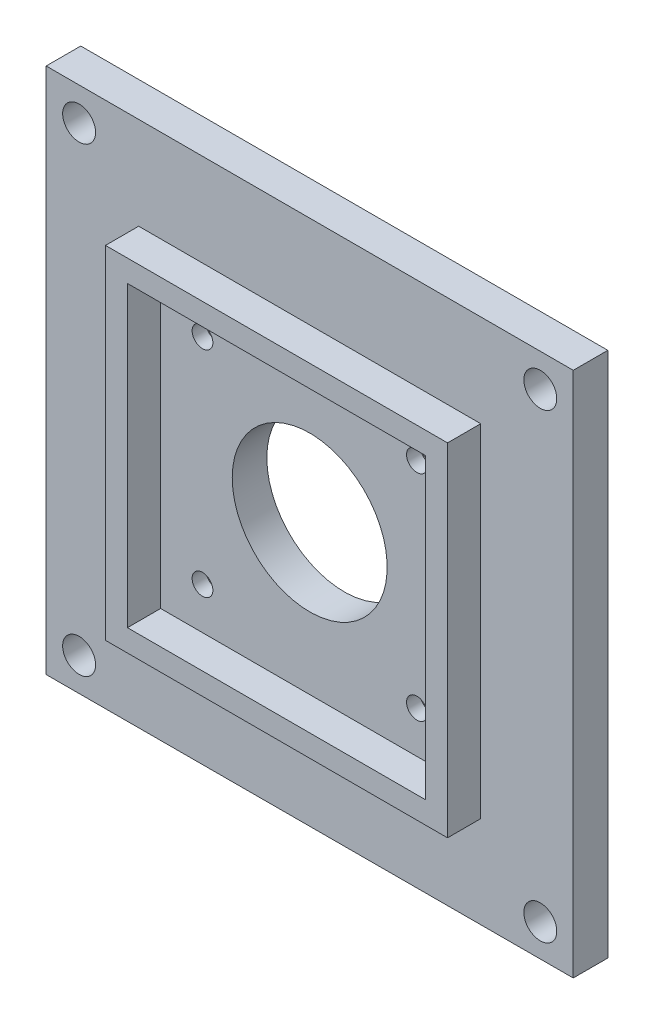
SolidWorks part; units mm, degrees
material "Pure Gold"
ref_plane "Front" through (0, 0, 0) normal (0, 0, 1) x (1, 0, 0)
ref_plane "Top" through (0, 0, 0) normal (0, 1, 0) x (1, 0, 0)
ref_plane "Right" through (0, 0, 0) normal (1, 0, 0) x (0, 0, -1)
sketch "Sketch4" plane through (0, 0, 0) normal (0, 0, 1) x (1, 0, 0)
  line L0 (0, -42.8625) -> (0, 41.275) construction
  line L1 (-49.15, -15.5) -> (-80.15, 15.5) construction
  line L2 (-80.15, -15.5) -> (-49.15, 15.5) construction
  line L3 (-39.925, 44.5615) -> (-39.925, -66.5635) construction
  line L4 (-71.275, 44.5615) -> (-71.275, -66.5635) construction
  line L8 (-62.05, 15.5) -> (-31.05, -15.5) construction
  line L9 (-31.05, 15.5) -> (-62.05, -15.5) construction
  line L11 (-31.05, 36.624) -> (-31.05, -53.8635) construction
  line L12 (43.75, 0) -> (-164.4633, 0) construction
  line L13 (-62.05, 36.624) -> (-62.05, -53.8635) construction
  line L14 (-49.15, 36.624) -> (-49.15, -53.8635) construction
  line L15 (-80.15, 36.624) -> (-80.15, -53.8635) construction
  line L16 (-113.2228, 15.5) -> (-0.2036, 15.5) construction
  line L17 (-113.2228, -15.5) -> (-0.2036, -15.5) construction
  line L18 (-25, -66.5635) -> (-25, 44.5615) construction
  line L19 (-68.1, -66.5635) -> (-68.1, 44.5615) construction
  line L20 (-43.1, 44.5615) -> (-43.1, -66.5635) construction
  line L21 (-86.2, -66.5635) -> (-86.2, 44.5615) construction
  line L22 (5.8397, -21.55) -> (-134.1626, -21.55) construction
  line L23 (5.8397, 21.55) -> (-134.1626, 21.55) construction
  line L24 (10.9249, -24.725) -> (-138.6228, -24.725) construction
  line L25 (10.9249, 24.725) -> (-138.6228, 24.725) construction
  line L26 (-89.375, 44.5615) -> (-89.375, -66.5635) construction
  line L27 (-21.825, 44.5615) -> (-21.825, -66.5635) construction
  circle A0 centre (0, 0) radius 12.7 construction
  circle A1 centre (0, 0) radius 15.875 construction
  circle A2 centre (0, 0) radius 9.46 construction
  circle A3 centre (-93.65, 0) radius 9.46 construction
  arc A4 (-93.65, 12.7) -> (-93.65, -12.7) centre (-93.65, 0) ccw construction
  circle A5 centre (27.27, 0) radius 9.46 construction
  circle A6 centre (27.27, 0) radius 12.7 construction
  circle A7 centre (-120.3675, 0) radius 9.46 construction
  circle A8 centre (-120.3675, 0) radius 12.7 construction
  point P3 (0, 0)
  point P6 (-49.15, -15.5)
  point P11 (-93.65, 0)
  point P12 (-49.15, 15.5)
  point P13 (-46.55, 0)
  point P14 (-80.15, 15.5)
  point P15 (-80.15, -15.5)
  point P61 (-64.65, 0)
  point P65 (27.27, 0)
  point P66 (-120.3675, 0)
  dimension "D20" = 3.175
  dimension "D18" = 29
  dimension "D26" = 73.82
  dimension "D27" = 64.65
  dimension "D2" = 31
  dimension "D3" = 25
  dimension "D4" = 31
  dimension "D5" = 21.825
  dimension "D6" = 15.5
  dimension "D7" = 15.5
  dimension "D8" = 6.05
  dimension "D9" = 6.05
  dimension "D10" = 6.05
  dimension "D11" = 6.05
  dimension "D12" = 6.05
  dimension "D13" = 6.05
  dimension "D14" = 3.175
  dimension "D15" = 3.175
  dimension "D16" = 3.175
  dimension "D17" = 3.175
  dimension "D19" = 3.175
  dimension "D21" = 3.175
  dimension "D22" = 46.55
  dimension "D23" = 47.1
  dimension "D24" = 58.32
  dimension "D25" = 147.6375
sketch "Sketch5" plane through (0, 0, 0) normal (0, 0, 1) x (1, 0, 0)
  line L0 (-25, -21.55) -> (-25, 21.55)
  line L1 (-25, -66.5635) -> (-25, 44.5615) construction
  line L2 (5.8397, -21.55) -> (-134.1626, -21.55) construction
  line L3 (5.8397, 21.55) -> (-134.1626, 21.55) construction
  line L4 (-25, 21.55) -> (-68.1, 21.55)
  line L6 (-68.1, -66.5635) -> (-68.1, 44.5615) construction
  line L7 (-68.1, 21.55) -> (-68.1, -21.55)
  line L8 (-68.1, -21.55) -> (-25, -21.55)
  line L9 (-21.825, 24.725) -> (-21.825, -24.725)
  line L10 (10.9249, 24.725) -> (-138.6228, 24.725) construction
  line L11 (-21.825, 44.5615) -> (-21.825, -66.5635) construction
  line L12 (10.9249, -24.725) -> (-138.6228, -24.725) construction
  line L13 (-21.825, -24.725) -> (-71.275, -24.725)
  line L14 (-71.275, 44.5615) -> (-71.275, -66.5635) construction
  line L15 (-71.275, -24.725) -> (-71.275, 24.725)
  line L16 (-71.275, 24.725) -> (-21.825, 24.725)
extrude "Extrude1" add sketch "Sketch5" along normal blind 4.8
sketch "Sketch6" plane through (0, 0, 0) normal (0, 0, -1) x (-1, 0, 0)
  line L0 (8.45, 83.4705) -> (8.45, -75.5808) construction
  line L1 (84.65, 274.6375) -> (84.65, -282.0493) construction
  line L2 (409.575, -38.1) -> (-293.1783, -38.1) construction
  line L3 (387.35, 38.1) -> (-330.5618, 38.1) construction
  line L4 (8.45, 38.1) -> (8.45, -37.987)
  line L5 (8.45, -37.987) -> (84.65, -38.1)
  line L6 (84.65, -38.1) -> (84.65, 38.1)
  line L7 (84.65, 38.1) -> (8.45, 38.1)
  line L8 (13.2125, 92.075) -> (13.2125, -77.5708) construction
  line L9 (79.8875, 88.9) -> (79.8875, -84.1375) construction
  line L10 (-44.45, 33.3375) -> (120.65, 33.3375) construction
  line L11 (-14.2875, -33.3375) -> (123.825, -33.3375) construction
  circle A0 centre (62.05, 15.5) radius 1.5
  circle A1 centre (31.05, 15.5) radius 1.5
  circle A2 centre (62.05, -15.5) radius 1.5
  circle A3 centre (31.05, -15.5) radius 1.5
  circle A4 centre (13.2125, 33.3375) radius 2.3812
  circle A5 centre (79.8875, 33.3375) radius 2.3813
  circle A6 centre (79.8875, -33.3094) radius 2.3813
  circle A7 centre (13.2125, -33.3375) radius 2.3812
  circle A8 centre (46.55, 0) radius 11.2
  dimension "D1" = 38.1
  dimension "D2" = 76.2
  dimension "D3" = 38.1
  dimension "D4" = 76.2
  dimension "D5" = 4.7625
  dimension "D6" = 4.7625
  dimension "D7" = 4.7625
  dimension "D8" = 4.7625
extrude "Extrude2" add sketch "Sketch6" along normal blind 5
sketch "Sketch7" plane through (0, 0, -5) normal (0, 0, -1) x (-1, 0, 0)
  circle A0 centre (31.05, 15.5) radius 6
  circle A1 centre (62.05, 15.5) radius 6
  circle A2 centre (62.05, -15.5) radius 6
  circle A3 centre (31.05, -15.5) radius 6
extrude "Extrude3" cut sketch "Sketch7" against normal blind 3
